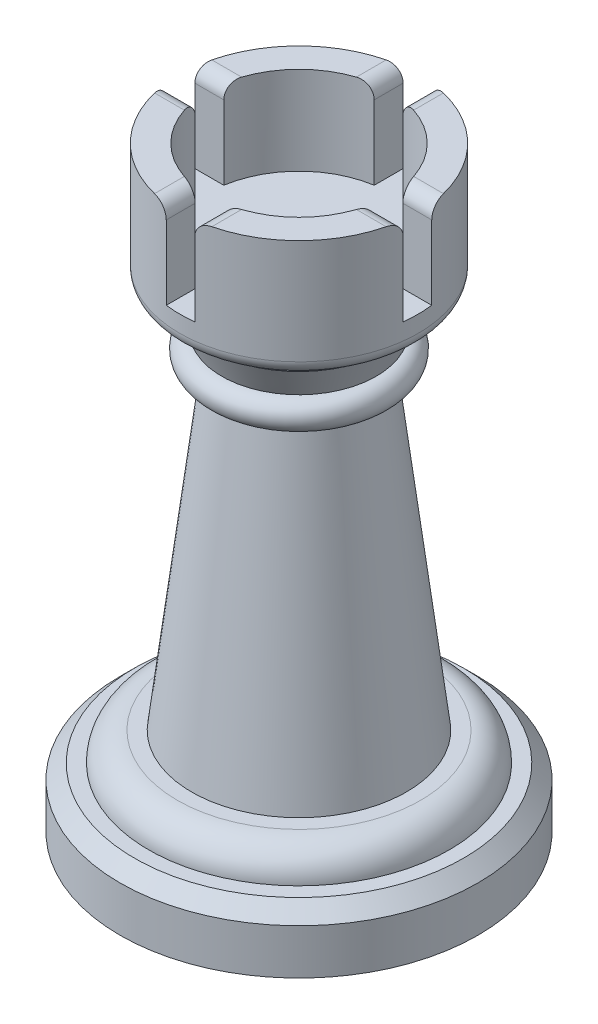
SolidWorks part; units mm, degrees
ref_plane "Front Plane" through (0, 0, 0) normal (0, 0, 1) x (1, 0, 0)
ref_plane "Top Plane" through (0, 0, 0) normal (0, 1, 0) x (1, 0, 0)
ref_plane "Right Plane" through (0, 0, 0) normal (1, 0, 0) x (0, 0, -1)
sketch "Sketch1" plane through (0, 0, 0) normal (0, 0, 1) x (1, 0, 0)
  line L0 (0, 0) -> (0, 31.75)
  line L1 (0, 31.75) -> (-6.35, 31.75)
  line L2 (-6.35, 31.75) -> (-6.35, 25.4)
  line L3 (-6.35, 25.4) -> (-4.826, 25.4)
  line L4 (-4.826, 25.4) -> (-4.826, 24.638)
  line L5 (-4.826, 24.638) -> (-4.1128, 23.0632)
  line L8 (-4.1128, 21.5392) -> (-3.683, 21.5392)
  line L9 (-3.683, 21.5392) -> (-5.715, 4.699)
  line L10 (-5.715, 4.699) -> (-8.001, 4.699)
  line L11 (-8.001, 4.699) -> (-8.001, 3.175)
  line L12 (-8.001, 3.175) -> (-9.525, 3.175)
  line L13 (-9.525, 3.175) -> (-9.525, 0)
  line L14 (-9.525, 0) -> (0, 0)
  arc A0 (-4.1128, 23.0632) -> (-4.1128, 21.5392) centre (-4.1128, 22.3012) ccw
  dimension "D11" = 0.4298
  dimension "D1" = 31.75
  dimension "D2" = 9.525
  dimension "D3" = 3.175
  dimension "D4" = 1.524
  dimension "D5" = 1.524
  dimension "D6" = 21.5392
  dimension "D7" = 6.35
  dimension "D8" = 6.35
  dimension "D9" = 1.524
  dimension "D10" = 1.524
  dimension "D12" = 0.762
  dimension "D13" = 3.683
  dimension "D15" = 2.286
revolve "Revolve1" add sketch "Sketch1" angle 360 about L0
chamfer "Chamfer1" distance 0.762 angle 45 1 edges at (0, 3.175, -9.525)
fillet "Fillet1" radius 0.762 2 edges at (0, 25.4, -4.826) (0, 25.4, -6.35)
sketch "Sketch2" plane through (0, 31.75, 0) normal (0, 1, 0) x (1, 0, 0)
  line L1 (-13.8131, 0.762) -> (13.8131, 0.762)
  line L2 (-13.8131, 0.762) -> (-13.8131, -0.762)
  line L3 (-13.8131, -0.762) -> (13.8131, -0.762)
  line L4 (13.8131, 0.762) -> (13.8131, -0.762)
  line L5 (-13.8131, 0.762) -> (13.8131, -0.762) construction
  line L6 (-13.8131, -0.762) -> (13.8131, 0.762) construction
  line L7 (-0.762, 10.4631) -> (0.762, 10.4631)
  line L8 (-0.762, 10.4631) -> (-0.762, -10.4631)
  line L9 (-0.762, -10.4631) -> (0.762, -10.4631)
  line L10 (0.762, 10.4631) -> (0.762, -10.4631)
  line L11 (-0.762, 10.4631) -> (0.762, -10.4631) construction
  line L12 (-0.762, -10.4631) -> (0.762, 10.4631) construction
  circle A0 centre (0, 0) radius 4.826
  circle A1 centre (0, 0) radius 6.35 construction
  circle M6 centre (0, 0) radius 6.35
  dimension "D1" = 1.524
  dimension "D2" = 1.524
  dimension "D3" = 1.524
extrude "Cut-Extrude4" cut sketch "Sketch2" against normal blind 4.699 contours L1 A0 L10 | L8 A0 L1 | L3 A0 L8 | L10 A0 L3 | A0 L1 L3 M6 | A0 L10 L8 M6 | A0 L3 L1 M6 | A0 L8 L10 M6 | L8 A0 L10 L3 | L10 L1 L8 L3 | L1 A0 L3 L8 | L10 A0 L8 L1 | L3 A0 L1 L10 region at (-5.5703, 31.75, 0) region at (-2.3808, 31.75, -2.3808) region at (-2.784, 31.75, 0) region at (0, 31.75, -5.5703) region at (0, 31.75, -2.784) region at (0, 31.75, 0) region at (-2.3808, 31.75, 2.3808) region at (0, 31.75, 5.5703) region at (2.3808, 31.75, -2.3808) region at (2.784, 31.75, 0) region at (0, 31.75, 2.784) region at (5.5703, 31.75, 0) region at (2.3808, 31.75, 2.3808)
fillet "Fillet2" radius 0.762 8 edges at (-0.762, 31.75, 5.5348) (0.762, 31.75, 5.5348) (5.5348, 31.75, 0.762) (5.5348, 31.75, -0.762) (0.762, 31.75, -5.5348) (-0.762, 31.75, -5.5348) (-5.5348, 31.75, -0.762) (-5.5348, 31.75, 0.762)
fillet "Fillet3" radius 1.524 1 edges at (0, 4.699, -8.001)
